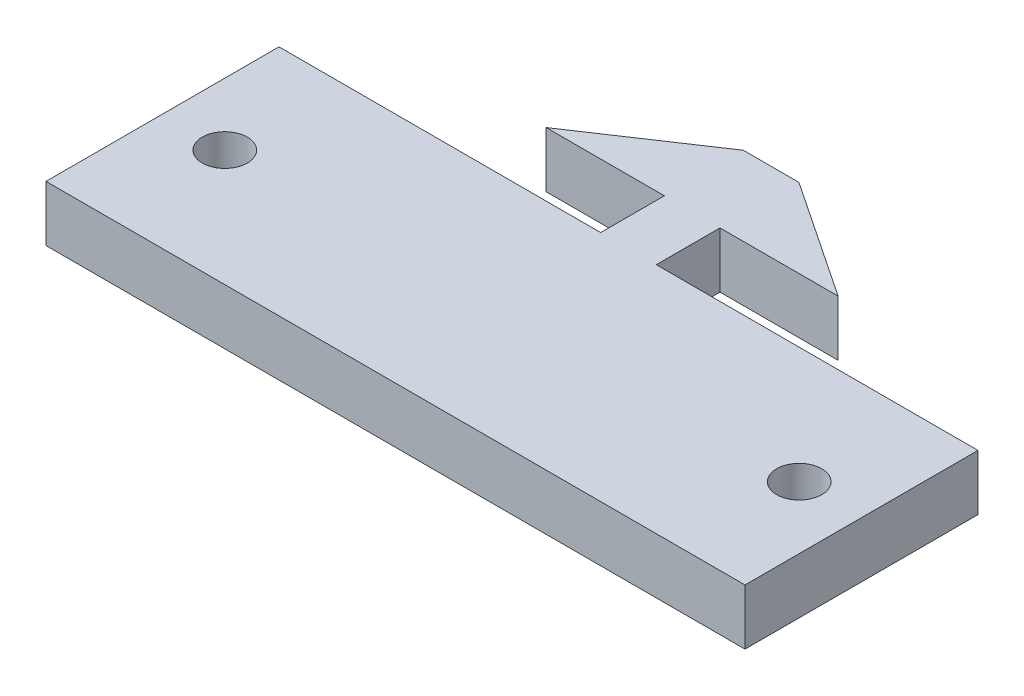
SolidWorks part; units mm, degrees
ref_plane "Front" through (0, 0, 0) normal (0, 0, 1) x (1, 0, 0)
ref_plane "Top" through (0, 0, 0) normal (0, 1, 0) x (1, 0, 0)
ref_plane "Right" through (0, 0, 0) normal (1, 0, 0) x (0, 0, -1)
sketch "Sketch1" plane through (0, 0, 0) normal (0, 1, 0) x (1, 0, 0)
  line L0 (-1.7907, 2.05) -> (-9.398, 2.05)
  line L2 (-1.7907, -2.05) -> (-1.7907, 2.05)
  line L4 (1.7907, -2.05) -> (1.7907, 2.05)
  line L7 (-9.398, 2.05) -> (-1.7907, 7.13)
  line L8 (-1.7907, 7.13) -> (1.7907, 7.13)
  line L9 (1.7907, 7.13) -> (9.398, 2.05)
  line L10 (9.398, 2.05) -> (1.7907, 2.05)
  line L11 (1.7907, -2.05) -> (22.5, -2.05)
  line L12 (-1.7907, -2.05) -> (-22.5, -2.05)
  line L13 (-22.5, -2.05) -> (-22.5, -17.05)
  line L14 (-22.5, -17.05) -> (22.5, -17.05)
  line L15 (22.5, -17.05) -> (22.5, -2.05)
  line L16 (22.5, -2.05) -> (1.7907, -2.05)
  point P0 (0, 0)
  point P17 (0, 7.13)
  point P19 (0, -17.05)
  point P24 (1.7907, 0)
  dimension "D1" = 18.796
  dimension "D2" = 3.5814
  dimension "D3" = 45
  dimension "D4" = 15
  dimension "D5" = 5.08
  dimension "D7" = 4.1
extrude "Boss-Extrude1" add sketch "Sketch1" along normal blind 3.5814 contours L14 L15 L11 L4 L10 L9 L8 L7 L0 L2 L12 L13 region at (0, 0, 8.3294)
sketch "Sketch2" plane through (0, 3.5814, 0) normal (0, 1, 0) x (1, 0, 0)
  line L0 (0, 0) -> (0, -15.3387) construction
  line L2 (-22.5, -2.05) -> (-22.5, -17.05) construction
  circle A0 centre (-18.49, -9.55) radius 1.45
  circle A1 centre (18.49, -9.55) radius 1.45
  point P11 (-22.5, -9.55)
  dimension "D1" = 2.9
  dimension "D2" = 18.49
extrude "Cut-Extrude1" cut sketch "Sketch2" against normal through all
